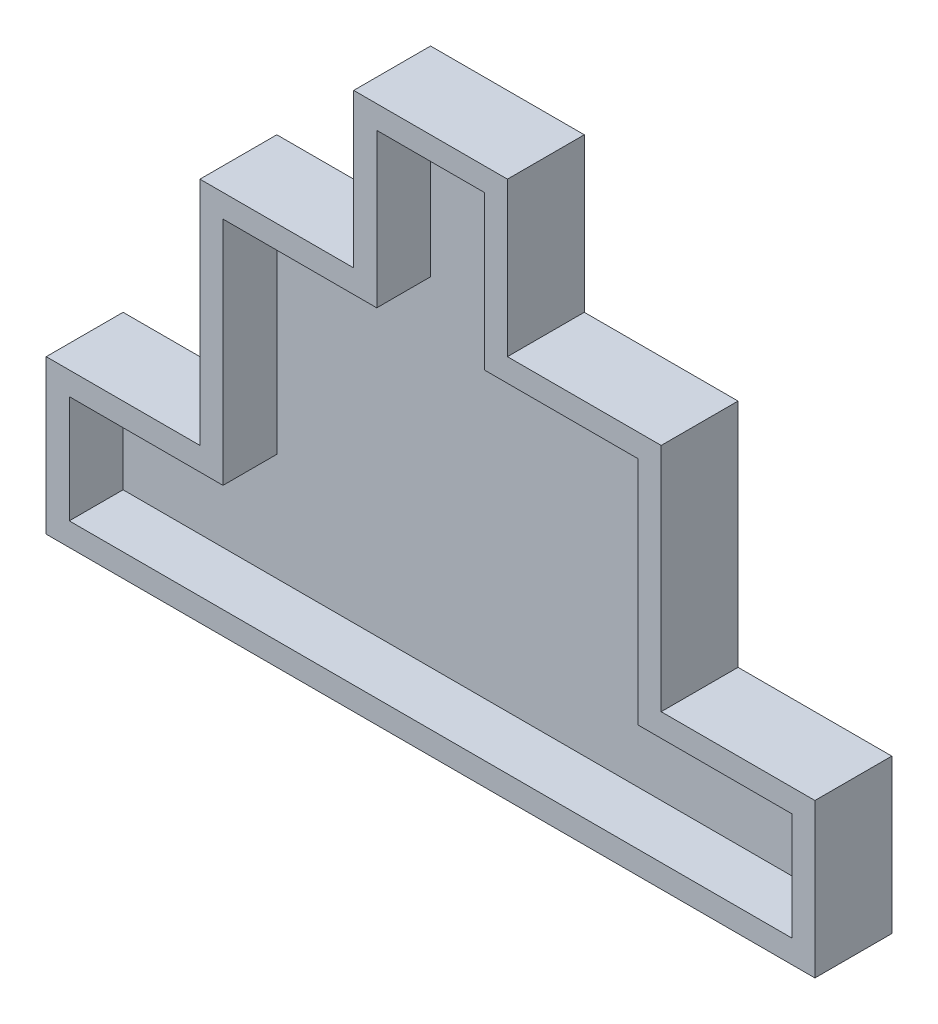
SolidWorks part; units mm, degrees
ref_plane "Front Plane" through (0, 0, 0) normal (0, 0, 1) x (1, 0, 0)
ref_plane "Top Plane" through (0, 0, 0) normal (0, 1, 0) x (1, 0, 0)
ref_plane "Right Plane" through (0, 0, 0) normal (1, 0, 0) x (0, 0, -1)
sketch "Sketch1" plane through (0, 0, 0) normal (0, 0, 1) x (1, 0, 0)
  line L0 (75, 0) -> (-75, 0)
  line L1 (-75, 0) -> (-75, 30)
  line L2 (-75, 30) -> (-45, 30)
  line L3 (-45, 30) -> (-45, 75)
  line L4 (-45, 75) -> (-15, 75)
  line L5 (-15, 75) -> (-15, 105)
  line L6 (-15, 105) -> (15, 105)
  line L7 (0, 0) -> (0, 209.0416) construction
  line L8 (15, 75) -> (15, 105)
  line L9 (45, 75) -> (15, 75)
  line L10 (45, 30) -> (45, 75)
  line L11 (75, 30) -> (45, 30)
  line L12 (75, 0) -> (75, 30)
  line L13 (-70.5, 4.5) -> (-70.5, 25.5)
  line L14 (-70.5, 25.5) -> (-40.5, 25.5)
  line L15 (-40.5, 25.5) -> (-40.5, 70.5)
  line L16 (-40.5, 70.5) -> (-10.5, 70.5)
  line L17 (-10.5, 70.5) -> (-10.5, 100.5)
  line L18 (-10.5, 100.5) -> (10.5, 100.5)
  line L19 (10.5, 70.5) -> (10.5, 100.5)
  line L20 (40.5, 70.5) -> (10.5, 70.5)
  line L21 (40.5, 25.5) -> (40.5, 70.5)
  line L22 (70.5, 25.5) -> (40.5, 25.5)
  line L23 (70.5, 4.5) -> (70.5, 25.5)
  line L24 (70.5, 4.5) -> (-70.5, 4.5)
  point P11 (0, 105)
  dimension "D1" = 30
  dimension "D2" = 45
  dimension "D3" = 30
  dimension "D4" = 30
  dimension "D5" = 30
  dimension "D6" = 15
  dimension "D7" = 4.5
extrude "Boss-Extrude1" add sketch "Sketch1" along normal blind 15
extrude "Boss-Extrude2" add sketch "Sketch1<2>" along normal blind 4.5 contours L13 L14 L15 L16 L17 L18 L19 L20 L21 L22 L23 L24
sketch "Sketch1<2>" plane through (0, 0, 0) normal (0, 0, 1) x (1, 0, 0) same geometry as "Sketch1"
